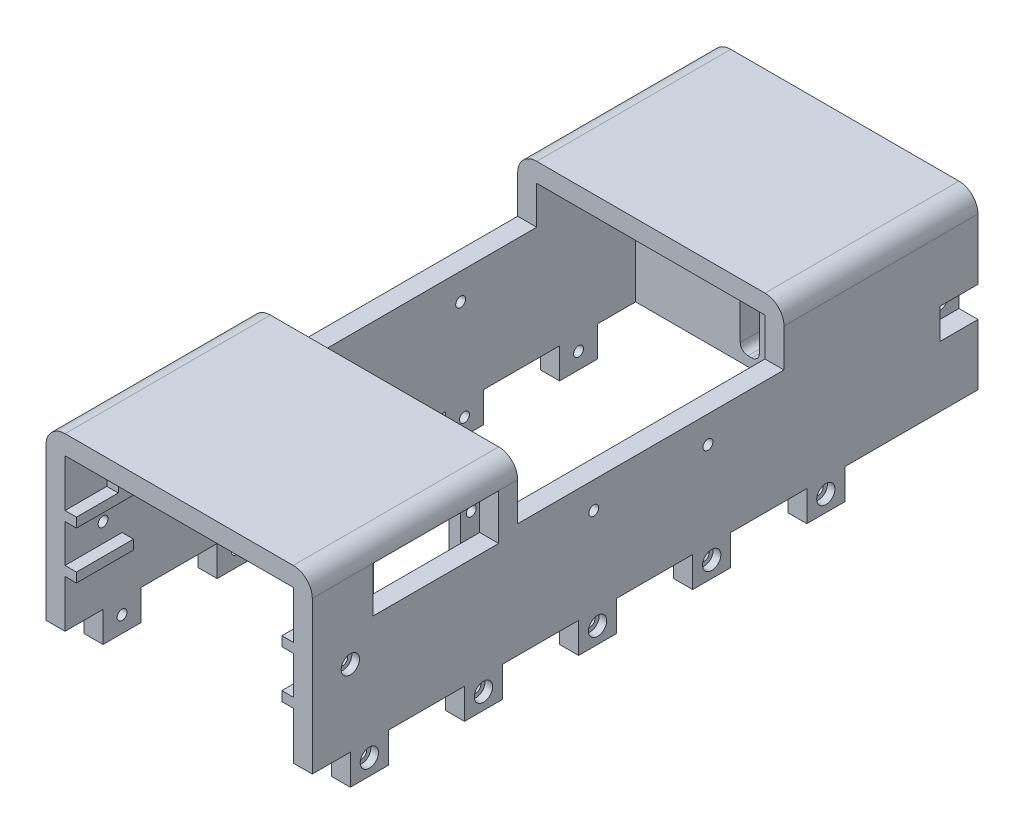
SolidWorks part; units mm, degrees
material "LW PLA"
ref_plane "Front Plane" through (0, 0, 0) normal (0, 0, 1) x (1, 0, 0)
ref_plane "Top Plane" through (0, 0, 0) normal (0, 1, 0) x (1, 0, 0)
ref_plane "Right Plane" through (0, 0, 0) normal (1, 0, 0) x (0, 0, -1)
sketch "Sketch1" plane through (0, 0, 0) normal (0, 1, 0) x (1, 0, 0)
  line L0 (-25, 0) -> (25, 0)
  line L1 (35, -185) -> (35, -10)
  line L2 (0, -25) -> (35, -25) construction
  line L3 (0, -35) -> (35, -35) construction
  line L4 (0, -95) -> (35, -95) construction
  line L5 (0, -175) -> (35, -175) construction
  line L6 (0, -20.35) -> (0, 20.35) construction
  line L7 (-35, -185) -> (-35, -10)
  line L8 (30, -185) -> (30, -10) construction
  line L9 (-30, -185) -> (-30, -10) construction
  arc A0 (35, -10) -> (25, 0) centre (25, -10) ccw
  arc A1 (-35, -10) -> (-25, 0) centre (-25, -10) cw
  point P20 (0, 0)
  dimension "D1" = 10
  dimension "D2" = 175
  dimension "D3" = 25
  dimension "D4" = 10
  dimension "D5" = 60
  dimension "D6" = 80
  dimension "D7" = 25
  dimension "D8" = 5
ref_plane "STA1" through (0, 0, 10) normal (0, 0, 1) x (1, 0, 0)
sketch "Body Arch" plane through (0, 0, 10) normal (0, 0, 1) x (1, 0, 0)
  line L0 (-30, 40) -> (30, 40)
  line L1 (-35, 0) -> (-30, 0)
  line L2 (-35, 0) -> (-35, 40)
  line L3 (-30, 45) -> (30, 45)
  line L4 (35, 0) -> (35, 40)
  line L5 (30, 0) -> (30, 40)
  line L7 (-30, 0) -> (-30, 40)
  line L8 (-30, 5) -> (30, 5) construction
  line L9 (-30, 5) -> (-30, 40) construction
  line L10 (30, 5) -> (30, 40) construction
  line L11 (30, 0) -> (35, 0)
  line L13 (-35, 0) -> (35, 0) construction
  arc A0 (35, 40) -> (30, 45) centre (30, 40) ccw
  arc A1 (-35, 40) -> (-30, 45) centre (-30, 40) cw
  arc A2 (30, 40) -> (30, 40) centre (30, 40) ccw
  arc A3 (-30, 40) -> (-30, 40) centre (-30, 40) cw
  point P9 (-35, 45)
  dimension "D2" = 5
  dimension "D1" = 45
  dimension "D3" = 5
sketch "Bulkhead" plane through (0, 0, 0) normal (0, 1, 0) x (1, 0, 0)
  line L0 (0, -35) -> (35, -35) construction
  line L1 (-30, -185) -> (-30, -10) construction
  line L2 (-30, -25) -> (30, -25)
  line L3 (-30, -25) -> (-30, -35)
  line L4 (-30, -35) -> (30, -35)
  line L5 (30, -25) -> (30, -35)
  line L6 (30, -185) -> (30, -10) construction
extrude "Boss-Extrude1" add sketch "Body Arch" along normal up to vertex (175 mm away) up to point (-35, 0, 185)
ref_plane "Plane1" through (35, 0, 0) normal (1, 0, 0) x (0, 0, -1)
sketch "Sketch2" plane through (35, 0, 0) normal (1, 0, 0) x (0, 0, -1)
  line L0 (-185, 0) -> (-10, 0) construction
  line L1 (-175, 0) -> (-165, 0)
  line L2 (-175, 0) -> (-175, -8)
  line L3 (-175, -8) -> (-165, -8)
  line L4 (-165, 0) -> (-165, -8)
  line L6 (-185, 0) -> (-10, 0) construction
  line L7 (-145, 0) -> (-145, -8)
  line L8 (-145, 0) -> (-135, 0)
  line L9 (-135, 0) -> (-135, -8)
  line L10 (-145, -8) -> (-135, -8)
  line L11 (-115, 0) -> (-115, -8)
  line L12 (-115, 0) -> (-105, 0)
  line L13 (-105, 0) -> (-105, -8)
  line L14 (-115, -8) -> (-105, -8)
  line L15 (-85, 0) -> (-85, -8)
  line L16 (-85, 0) -> (-75, 0)
  line L17 (-75, 0) -> (-75, -8)
  line L18 (-85, -8) -> (-75, -8)
  line L19 (-55, 0) -> (-55, -8)
  line L20 (-55, 0) -> (-45, 0)
  line L21 (-45, 0) -> (-45, -8)
  line L22 (-55, -8) -> (-45, -8)
  circle A0 centre (-170, -3.75) radius 1.3
  circle A1 centre (-170, -3.75) radius 2.4
  circle A2 centre (-140, -3.75) radius 2.4
  circle A3 centre (-140, -3.75) radius 1.3
  circle A4 centre (-110, -3.75) radius 2.4
  circle A5 centre (-110, -3.75) radius 1.3
  circle A6 centre (-80, -3.75) radius 2.4
  circle A7 centre (-80, -3.75) radius 1.3
  circle A8 centre (-50, -3.75) radius 2.4
  circle A9 centre (-50, -3.75) radius 1.3
  point P12 (-170, 0)
  dimension "D4" = 2.6
  dimension "D6" = 4.8
  dimension "D1" = 10
  dimension "D2" = 8
  dimension "D3" = 10
  dimension "D5" = 3.75
  dimension "D7" = 5
extrude "Boss-Extrude2" add sketch "Sketch2" against normal blind 5 contours L4 L1 L2 L3 A1 | L7 L10 L9 L8 A2 | L11 L14 L13 L12 A4 | L15 L18 L17 L16 A6 | L19 L22 L21 L20 A8 | A1 A0 | A2 A3 | A4 A5 | A6 A7 | A8 A9 region at (35, -0.1281, 170) region at (35, -0.1281, 140) region at (35, -0.1281, 110) region at (35, -0.1281, 80) region at (35, -0.1281, 50) region at (35, -3.75, 172.3321) region at (35, -3.75, 142.3321) region at (35, -3.75, 112.3321) region at (35, -3.75, 82.3321) region at (35, -3.75, 52.3321)
extrude "Cut-Extrude1" cut sketch "Sketch2<3>" against normal blind 2 contours A1 A0 | A2 A3 | A4 A5 | A6 A7 | A8 A9 region at (35, -3.75, 172.3321) region at (35, -3.75, 142.3321) region at (35, -3.75, 112.3321) region at (35, -3.75, 82.3321) region at (35, -3.75, 52.3321)
sketch "Sketch2<3>" plane through (35, 0, 0) normal (1, 0, 0) x (0, 0, -1) same geometry as "Sketch2"
mirror "Mirror1" about plane through (0, 0, 0) normal (1, 0, 0) of "Cut-Extrude1", "Boss-Extrude2"
sketch "Sketch4" plane through (30, 0, 0) normal (-1, 0, 0) x (0, 0, 1)
  line L0 (10, 40) -> (10, 0) construction
  line L1 (10, 26) -> (22, 26)
  line L2 (10, 26) -> (10, 14)
  line L3 (10, 14) -> (22, 14)
  line L4 (22, 26) -> (22, 14)
  circle A1 centre (15, 20) radius 1.95
  point P6 (10, 20)
  point P7 (10, 20)
  point P13 (22, 20)
  dimension "D3" = 3.9
  dimension "D1" = 12
  dimension "D2" = 12
  dimension "D4" = 5
extrude "Boss-Extrude3" add sketch "Sketch4" along normal blind 5
sketch "Sketch6" plane through (0, 0, 10) normal (0, 0, -1) x (-1, 0, 0)
  line L0 (-35, 0) -> (-35, 40) construction
  line L1 (-35, 24) -> (-30, 24)
  line L2 (-35, 24) -> (-35, 16)
  line L3 (-35, 16) -> (-30, 16)
  line L4 (-30, 24) -> (-30, 16)
  point P6 (-35, 20)
  point P7 (-35, 20)
  dimension "D1" = 5
  dimension "D2" = 8
extrude "Cut-Extrude4" cut sketch "Sketch6" against normal blind 10
mirror "Mirror2" about plane through (0, 0, 0) normal (1, 0, 0) of "Cut-Extrude4", "Boss-Extrude3"
ref_plane "Plane2" through (0, 45, 0) normal (0, 1, 0) x (1, 0, 0)
sketch "Sketch7" plane through (0, 45, 0) normal (0, 1, 0) x (1, 0, 0)
  line L0 (-35, -185) -> (-35, -10) construction
  line L1 (-35, -61) -> (35, -61)
  line L2 (-35, -61) -> (-35, -131)
  line L3 (-35, -131) -> (35, -131)
  line L4 (35, -61) -> (35, -131)
  line L5 (35, -185) -> (35, -10) construction
  line L6 (30, -185) -> (-30, -185) construction
  dimension "D1" = 70
  dimension "D2" = 54
extrude "Cut-Extrude5" cut sketch "Sketch7" against normal blind 15
sketch "Sketch9" plane through (35, 0, 0) normal (1, 0, 0) x (0, 0, -1)
  line L0 (-131, 30) -> (-61, 30) construction
  circle A0 centre (-81, 23) radius 1.3
  circle A4 centre (-111, 23) radius 1.3
  dimension "D3" = 2.6
  dimension "D4" = 2
  dimension "D1" = 7
  dimension "D2" = 20
extrude "Cut-Extrude6" cut sketch "Sketch9" against normal up to next contours A0 | A4
mirror "Mirror4" about plane through (0, 0, 0) normal (1, 0, 0) of "Cut-Extrude6"
sketch "Sketch10" plane through (0, 0, 0) normal (1, 0, 0) x (0, 0, -1)
  line L0 (-185, 40) -> (-195, 40)
  line L1 (-185, 40) -> (-165, 40)
  line L3 (-185, 35) -> (-165, 35)
  line L4 (-165, 40) -> (-165, 35)
  line L6 (-195, 40) -> (-195, 35)
  line L7 (-195, 35) -> (-185, 35)
  dimension "D1" = 20
  dimension "D2" = 5
  dimension "D3" = 10
sketch "Sketch13" plane through (-30, 0, 0) normal (1, 0, 0) x (0, 0, -1)
  line L5 (-185, 0) -> (-185, 40) construction
  line L10 (-185, 30) -> (-165, 30)
  line L11 (-185, 30) -> (-185, 10)
  line L12 (-185, 10) -> (-165, 10)
  line L13 (-165, 30) -> (-165, 10)
  line L15 (-185, 30) -> (-195, 30)
  line L16 (-185, 30) -> (-185, 10)
  line L17 (-185, 10) -> (-195, 10)
  line L18 (-195, 30) -> (-195, 10)
  point P6 (-185, 20)
  point P7 (-185, 20)
  dimension "D1" = 20
  dimension "D2" = 20
  dimension "D3" = 10
sketch "Sketch18" plane through (35, 0, 0) normal (1, 0, 0) x (0, 0, -1)
  line L0 (-185, 30) -> (-185, 10) construction
  line L2 (-185, 40) -> (-131, 40) construction
  circle A0 centre (-175, 20) radius 1.3
  circle A1 centre (-175, 20) radius 2.4
  dimension "D3" = 4.8
  dimension "D4" = 2.6
  dimension "D1" = 10
  dimension "D2" = 20
extrude "Cut-Extrude15" cut sketch "Sketch18" against normal up to next contours A0
extrude "Cut-Extrude16" cut sketch "Sketch18<3>" against normal blind 2 contours A1
sketch "Sketch18<3>" plane through (35, 0, 0) normal (1, 0, 0) x (0, 0, -1) same geometry as "Sketch18"
mirror "Mirror6" about plane through (0, 0, 0) normal (1, 0, 0) of "Cut-Extrude15", "Cut-Extrude16"
extrude "Boss-Extrude4" add sketch "Bulkhead" along normal up to next
sketch "Sketch20" plane through (-35, 0, 0) normal (-1, 0, 0) x (0, 0, 1)
  line L0 (131, 30) -> (131, 40) construction
  line L1 (136, 40) -> (169, 40)
  line L2 (136, 40) -> (136, 28)
  line L3 (136, 28) -> (169, 28)
  line L4 (169, 40) -> (169, 28)
  line L5 (185, 40) -> (131, 40) construction
  dimension "D1" = 33
  dimension "D2" = 12
  dimension "D3" = 5
extrude "Cut-Extrude17" cut sketch "Sketch20" against normal up to next
sketch "Sketch21" plane through (-30, 0, 0) normal (1, 0, 0) x (0, 0, -1)
  line L0 (-168.8, 34) -> (-136.2, 34) construction
  line L1 (-169, 28) -> (-136, 28) construction
  line L2 (-169, 40) -> (-169, 28) construction
  line L3 (-152.5, 34) -> (-152.5, 28) construction
  line L4 (-131, 40) -> (-141.1, 40)
  line L5 (-131, 40) -> (-131, 25)
  line L6 (-131, 25) -> (-141.1, 25)
  line L7 (-141.1, 40) -> (-141.1, 25)
  line L8 (-174, 25) -> (-163.9, 25)
  line L9 (-163.9, 40) -> (-163.9, 25)
  line L10 (-174, 40) -> (-163.9, 40)
  line L11 (-174, 40) -> (-174, 25)
  circle A0 centre (-138.2, 34) radius 1.3
  circle A1 centre (-166.8, 34) radius 1.3
  point P4 (-152.5, 28)
  point P5 (-152.5, 34)
  point P8 (-169, 34)
  dimension "D4" = 2.6
  dimension "D1" = 32.6
  dimension "D2" = 4.9
  dimension "D3" = 2
  dimension "D5" = 28.6
  dimension "D6" = 15
extrude "Boss-Extrude6" add sketch "Sketch21" along normal blind 3
sketch "Sketch22" plane through (0, 0, 25) normal (0, 0, -1) x (-1, 0, 0)
  line L0 (0, 29.15) -> (0, -29.15) construction
  line L1 (-25, 14) -> (-25, 26) construction
  line L3 (-15.5, 22.5) -> (15.5, 22.5)
  line L4 (-17.5, 20.5) -> (-17.5, 19.5)
  line L5 (-15.5, 17.5) -> (15.5, 17.5)
  line L6 (17.5, 20.5) -> (17.5, 19.5)
  line L7 (-0.5, 37.5) -> (0.5, 37.5)
  line L8 (-2.5, 35.5) -> (-2.5, 4.5)
  line L9 (-0.5, 2.5) -> (0.5, 2.5)
  line L10 (2.5, 35.5) -> (2.5, 4.5)
  arc A0 (15.5, 17.5) -> (17.5, 19.5) centre (15.5, 19.5) ccw
  arc A1 (17.5, 20.5) -> (15.5, 22.5) centre (15.5, 20.5) ccw
  arc A2 (-17.5, 19.5) -> (-15.5, 17.5) centre (-15.5, 19.5) ccw
  arc A3 (-17.5, 20.5) -> (-15.5, 22.5) centre (-15.5, 20.5) cw
  arc A4 (0.5, 2.5) -> (2.5, 4.5) centre (0.5, 4.5) ccw
  arc A5 (-0.5, 2.5) -> (-2.5, 4.5) centre (-0.5, 4.5) cw
  arc A6 (0.5, 37.5) -> (2.5, 35.5) centre (0.5, 35.5) cw
  arc A7 (-0.5, 37.5) -> (-2.5, 35.5) centre (-0.5, 35.5) ccw
  point P8 (-17.5, 20)
  point P11 (0, 22.5)
  point P14 (-2.5, 20)
  point P15 (0, 37.5)
  point P18 (17.5, 17.5)
  point P21 (17.5, 22.5)
  point P26 (-17.5, 22.5)
  point P29 (2.5, 2.5)
  point P32 (-2.5, 2.5)
  point P37 (-2.5, 37.5)
  point P38 (-25, 20)
  line M10 (30, 40) -> (-30, 40)
  dimension "D2" = 5
  dimension "D6" = 2
  dimension "D3" = 5
  dimension "D4" = 35
  dimension "D5" = 35
extrude "Cut-Extrude18" cut sketch "Sketch22" along direction (0, 0, -1) on the side against the normal up to next (10 mm away) contours A3 L4 A2 L5 L8 L3 | A5 L9 A4 L10 L5 L8 | L6 A1 L3 L10 L5 A0 | L10 L3 L8 L5 | A7 L8 L3 L10 A6 M10 region at (9.8348, 20, 25) region at (0, 29.8348, 25) region at (0, 20, 25) region at (-9.8348, 20, 25) region at (0, 10.1652, 25)
sketch "Sketch23" plane through (-30, 0, 0) normal (1, 0, 0) x (0, 0, -1)
  line L0 (-185, 0) -> (-185, 40) construction
  line L1 (-174, 25) -> (-185, 25)
  line L2 (-174, 25) -> (-174, 27.5)
  line L3 (-174, 27.5) -> (-185, 27.5)
  line L4 (-185, 25) -> (-185, 27.5)
  line L6 (-185, 15) -> (-170, 15)
  line L7 (-185, 15) -> (-185, 12.5)
  line L8 (-185, 12.5) -> (-170, 12.5)
  line L9 (-170, 15) -> (-170, 12.5)
  dimension "D1" = 2.5
  dimension "D2" = 15
  dimension "D3" = 2.5
  dimension "D4" = 10
extrude "Boss-Extrude7" add sketch "Sketch23" along normal blind 3
mirror "Mirror7" about plane through (0, 0, 0) normal (1, 0, 0) of "Boss-Extrude7", "Cut-Extrude17", "Boss-Extrude6"
